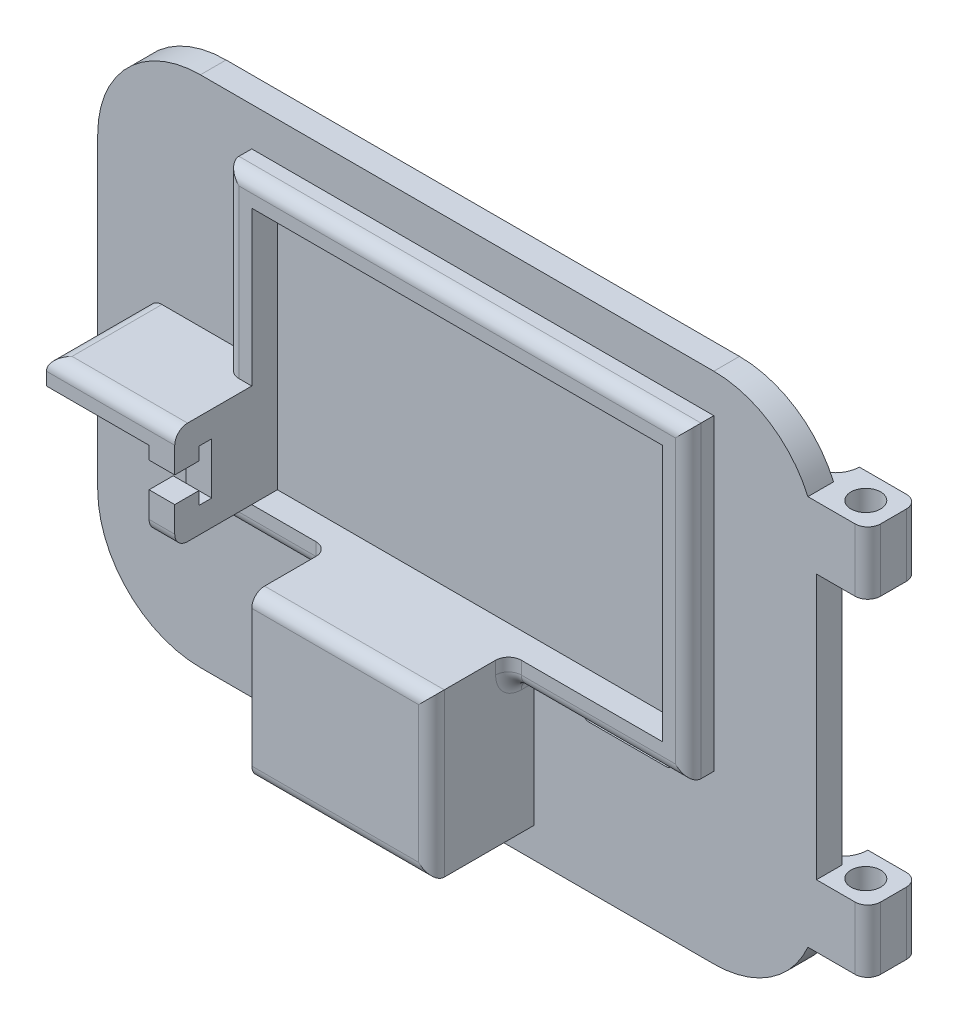
SolidWorks part; units mm, degrees
ref_plane "Front Plane" through (0, 0, 0) normal (0, 0, 1) x (1, 0, 0)
ref_plane "Top Plane" through (0, 0, 0) normal (0, 1, 0) x (1, 0, 0)
ref_plane "Right Plane" through (0, 0, 0) normal (1, 0, 0) x (0, 0, -1)
sketch "Sketch1" plane through (0, 0, 0) normal (0, 0, 1) x (1, 0, 0)
  line L0 (-63.5, 63.5) -> (63.5, 63.5)
  line L1 (63.5, -63.5) -> (-63.5, -63.5)
  line L2 (-88.9, -38.1) -> (-88.9, 38.1)
  line L3 (88.9, -38.1) -> (88.9, 38.1)
  arc A0 (-88.9, 38.1) -> (-63.5, 63.5) centre (-63.5, 38.1) cw
  arc A1 (-63.5, -63.5) -> (-88.9, -38.1) centre (-63.5, -38.1) cw
  arc A2 (63.5, -63.5) -> (88.9, -38.1) centre (63.5, -38.1) ccw
  arc A3 (88.9, 38.1) -> (63.5, 63.5) centre (63.5, 38.1) ccw
  dimension "D1" = 25.4
  dimension "D2" = 88.9
  dimension "D3" = 88.9
  dimension "D4" = 63.5
  dimension "D5" = 63.5
extrude "Boss-Extrude1" add sketch "Sketch1" against normal blind 6.35
sketch "Sketch3" plane through (0, 0, 0) normal (0, 0, 1) x (1, 0, 0)
  line L0 (63.5, 63.5) -> (88.9, 63.5) construction
  line L1 (88.9, 63.5) -> (101.6, 63.5) construction
  line L6 (101.6, 32.75) -> (101.6, 48.26)
  line L8 (101.6, 48.26) -> (86.7795, 48.26)
  line L9 (101.6, 63.5) -> (101.6, 32.75) construction
  line L10 (101.6, 32.75) -> (88.9, 32.75)
  line L11 (88.9, -38.1) -> (88.9, 38.1) construction
  line L12 (88.9, 32.75) -> (88.9, 38.1)
  arc A0 (88.9, 38.1) -> (86.7795, 48.26) centre (63.5, 38.1) ccw
  dimension "D5" = 25.4
  dimension "D1" = 25.4
  dimension "D2" = 12.7
  dimension "D3" = 30.75
  dimension "D4" = 15.24
extrude "Boss-Extrude2" add sketch "Sketch3" against normal blind 12.7
sketch "Sketch4" plane through (0, 48.26, 0) normal (0, 1, 0) x (1, 0, 0)
  line L0 (101.6, 6.35) -> (94.75, 6.35) construction
  line L1 (101.6, 12.7) -> (101.6, 0) construction
  circle A0 centre (94.75, 6.35) radius 3.675
  point P6 (98.425, 6.35)
  dimension "D1" = 7.35
  dimension "D2" = 3.175
extrude "Cut-Extrude2" cut sketch "Sketch4" against normal up to next
sketch "Sketch5" plane through (0, 0, 0) normal (0, 0, 1) x (1, 0, 0)
  line L0 (0, 0) -> (88.9402, 0)
mirror "Mirror1" about plane through (0, 0, 0) normal (0, 1, 0) of "Cut-Extrude2", "Boss-Extrude2"
sketch "Sketch7" plane through (0, 0, -6.35) normal (0, 0, -1) x (-1, 0, 0)
  line L0 (0, 0) -> (57.15, 0) construction
  point P4 (57.15, 0)
  dimension "D1" = 57.15
ref_plane "Plane1" through (-57.15, 0, -6.35) normal (-1, 0, 0) x (0, 0, 1)
sketch "Sketch8" plane through (-57.15, 0, -6.35) normal (-1, 0, 0) x (0, 0, 1)
  line L0 (0, 0) -> (0, 38.1) construction
  line L1 (0, 38.1) -> (0, 44.45)
  line L2 (-19.05, 25.4) -> (-19.05, -25.4)
  line L3 (0, 24.7494) -> (-24.0575, 24.7494) construction
  line L4 (-12.7, 25.4) -> (-12.7, 40.5526) construction
  line L5 (-19.05, 0) -> (-12.7, 0) construction
  line L6 (-12.7, -25.4) -> (-12.7, 25.4)
  line L7 (0, -38.1) -> (0, -44.45)
  arc A0 (0, 44.45) -> (-19.05, 25.4) centre (0, 25.4) ccw
  arc A1 (0, 38.1) -> (-12.7, 25.4) centre (0, 25.4) ccw
  arc A2 (0, -38.1) -> (-12.7, -25.4) centre (0, -25.4) cw
  arc A3 (0, -44.45) -> (-19.05, -25.4) centre (0, -25.4) cw
  dimension "D1" = 38.1
  dimension "D2" = 6.35
  dimension "D3" = 19.7006
  dimension "D4" = 12.7
extrude "Boss-Extrude3" add sketch "Sketch8" against normal blind 12.7
fillet "Fillet1" radius 6.35 1 edges at (-50.8, -44.45, -6.35)
fillet "Fillet2" radius 6.35 1 edges at (-57.15, -44.0467, -6.35)
fillet "Fillet3" radius 6.35 1 edges at (-44.45, -44.0467, -6.35)
fillet "Fillet4" radius 6.35 3 edges at (-50.8, 44.45, -6.35) (-44.45, 41.275, -6.35) (-57.15, 41.275, -6.35)
sketch "Sketch9" plane through (0, 0, 0) normal (0, 0, 1) x (1, 0, 0)
  line L0 (88.9402, 0) -> (-88.9, 0) construction
  line L1 (-88.9, 38.1) -> (-88.9, -38.1) construction
  line L22 (57.15, 47.625) -> (-44.45, 47.625)
  line L23 (57.15, 47.625) -> (57.15, -15.875)
  line L24 (57.15, -15.875) -> (-44.45, -15.875)
  line L25 (-44.45, 47.625) -> (-44.45, -15.875)
  line L26 (-63.5, -63.5) -> (63.5, -63.5) construction
  line L28 (63.5, 53.975) -> (63.5, -22.225)
  line L29 (63.5, -22.225) -> (-50.8, -22.225)
  line L30 (-50.8, 53.975) -> (-50.8, -22.225)
  line L31 (63.5, 53.975) -> (-50.8, 53.975)
  dimension "D1" = 63.5
  dimension "D2" = 101.6
  dimension "D3" = 47.625
  dimension "D4" = 38.1
  dimension "D5" = 6.35
extrude "Boss-Extrude4" add sketch "Sketch9" along normal blind 6.35
sketch "Sketch10" plane through (0, 0, 0) normal (0, 0, 1) x (1, 0, 0)
  line L0 (-44.45, 47.625) -> (-44.45, 10.9459) construction
  line L1 (57.15, -15.875) -> (57.15, -25.527) construction
  line L2 (32.639, -25.527) -> (51.689, -25.527) construction
  line L3 (32.639, -23.9395) -> (51.689, -23.9395)
  line L4 (32.639, -27.1145) -> (51.689, -27.1145)
  line L5 (57.15, -25.527) -> (42.164, -25.527) construction
  arc A0 (32.639, -23.9395) -> (32.639, -27.1145) centre (32.639, -25.527) ccw
  arc A1 (51.689, -27.1145) -> (51.689, -23.9395) centre (51.689, -25.527) ccw
  point P6 (42.164, -25.527)
  dimension "D1" = 9.652
  dimension "D2" = 14.986
  dimension "D3" = 19.05
  dimension "D4" = 3.175
extrude "Cut-Extrude3" cut sketch "Sketch10" against normal up to next
sketch "Sketch14" plane through (0, 0, 0) normal (0, 0, 1) x (1, 0, 0)
  line L0 (12.7, -22.225) -> (12.7, -49.657)
  line L1 (-50.8, -22.225) -> (63.5, -22.225) construction
  line L2 (12.7, -49.657) -> (-25.4, -49.657)
  line L3 (63.5, -22.225) -> (63.5, 53.975) construction
  line L4 (19.05, -22.225) -> (19.05, -56.007)
  line L5 (19.05, -56.007) -> (-25.4, -56.007)
  line L6 (-25.4, -56.007) -> (-25.4, -49.657)
  line L7 (19.05, -15.875) -> (-25.4, -15.875)
  line L8 (-44.45, -15.875) -> (57.15, -15.875) construction
  line L9 (-25.4, -15.875) -> (-25.4, -22.225)
  line L10 (-25.4, -22.225) -> (12.7, -22.225)
  line L11 (19.05, -22.225) -> (19.05, -15.875)
  dimension "D1" = 38.1
  dimension "D2" = 27.432
  dimension "D3" = 50.8
  dimension "D4" = 6.35
extrude "Boss-Extrude7" add sketch "Sketch14" along normal blind 25.4
sketch "Sketch15" plane through (0, -49.657, 0) normal (0, 1, 0) x (1, 0, 0)
  line L0 (-25.4, -25.4) -> (-25.4, -19.05)
  line L1 (-25.4, -25.4) -> (-25.4, 0) construction
  line L2 (-25.4, -19.05) -> (12.7, -19.05)
  line L3 (12.7, -25.4) -> (12.7, 0) construction
  line L4 (12.7, -19.05) -> (12.7, -25.4)
  line L5 (12.7, -25.4) -> (-25.4, -25.4)
  dimension "D1" = 6.35
extrude "Boss-Extrude8" add sketch "Sketch15" along normal up to next
sketch "Sketch16" plane through (0, 0, 0) normal (0, 0, 1) x (1, 0, 0)
  line L0 (-50.8, 3.175) -> (-76.2, 3.175)
  line L1 (-50.8, 53.975) -> (-50.8, -22.225) construction
  line L2 (63.5, 53.975) -> (-50.8, 53.975) construction
  line L3 (-76.2, 9.525) -> (-76.2, 3.175)
  line L4 (-50.8, 9.525) -> (-44.45, 9.525)
  line L5 (-44.45, 47.625) -> (-44.45, -15.875) construction
  line L6 (-44.45, 9.525) -> (-44.45, -15.875)
  line L7 (-44.45, -15.875) -> (-50.8, -15.875)
  line L8 (-50.8, -15.875) -> (-50.8, 3.175)
  line L9 (-44.45, -15.875) -> (-25.4, -15.875) construction
  line L13 (-50.8, 9.525) -> (-76.2, 9.525)
  point P8 (-47.625, -15.875)
  dimension "D1" = 25.4
  dimension "D2" = 50.8
  dimension "D3" = 6.35
extrude "Boss-Extrude9" add sketch "Sketch16" along normal blind 25.4
sketch "Sketch17" plane through (-50.8, 0, 0) normal (-1, 0, 0) x (0, 0, 1)
  line L0 (0, 3.175) -> (16.256, 3.175) construction
  line L1 (0, 3.175) -> (25.4, 3.175) construction
  line L2 (16.256, 3.175) -> (16.256, -9.525)
  line L3 (16.256, -9.525) -> (19.431, -9.525)
  line L4 (19.431, -9.525) -> (19.431, 3.175)
  line L5 (19.431, 3.175) -> (16.256, 3.175)
  dimension "D1" = 16.256
  dimension "D2" = 12.7
  dimension "D3" = 3.175
extrude "Cut-Extrude4" cut sketch "Sketch17" against normal up to next
sketch "Sketch18" plane through (0, 0, 25.4) normal (0, 0, 1) x (1, 0, 0)
  line L0 (-50.8, 0) -> (-44.45, 0) construction
  line L1 (-44.45, -15.875) -> (-44.45, 9.525) construction
  line L4 (-50.8, 3.175) -> (-50.8, -15.875) construction
  line L5 (-44.45, 0) -> (-50.8, 0)
  line L6 (-44.45, 0) -> (-44.45, -6.35)
  line L7 (-44.45, -6.35) -> (-50.8, -6.35)
  line L8 (-50.8, 0) -> (-50.8, -6.35)
  line L9 (-44.45, 0) -> (-50.8, -6.35) construction
  line L10 (-44.45, -6.35) -> (-50.8, 0) construction
  line L11 (-44.45, 47.625) -> (-44.45, -15.875) construction
  line L12 (-76.2, 3.175) -> (-50.8, 3.175) construction
  dimension "D1" = 6.35
  dimension "D2" = 3.175
extrude "Cut-Extrude5" cut sketch "Sketch18" against normal up to next
fillet "Fillet6" radius 3.175 16 edges at (19.05, -35.941, 25.4) (-3.175, -15.875, 25.4) (-3.175, -56.007, 25.4) (-25.4, -22.225, 12.7) (19.05, -22.225, 3.175) (-50.8, 31.75, 6.35) (-50.8, -19.05, 6.35) (-38.1, -22.225, 6.35) (41.275, -22.225, 6.35) (63.5, 15.875, 6.35) (6.35, 53.975, 6.35) (-25.4, -19.05, 6.35) (19.05, -19.05, 6.35) (-76.2, 9.525, 12.7) (-60.325, 9.525, 25.4) (-47.625, -15.875, 25.4)
fillet "Fillet9" radius 6.35 4 edges at (88.9, -35.425, -6.35) (88.9, 35.425, -6.35) (88.3642, -43.2895, -6.35) (88.3642, 43.2895, -6.35)
fillet "Fillet10" radius 3.175 4 edges at (101.6, 40.505, -12.7) (101.6, 40.505, 0) (101.6, -40.505, 0) (101.6, -40.505, -12.7)
